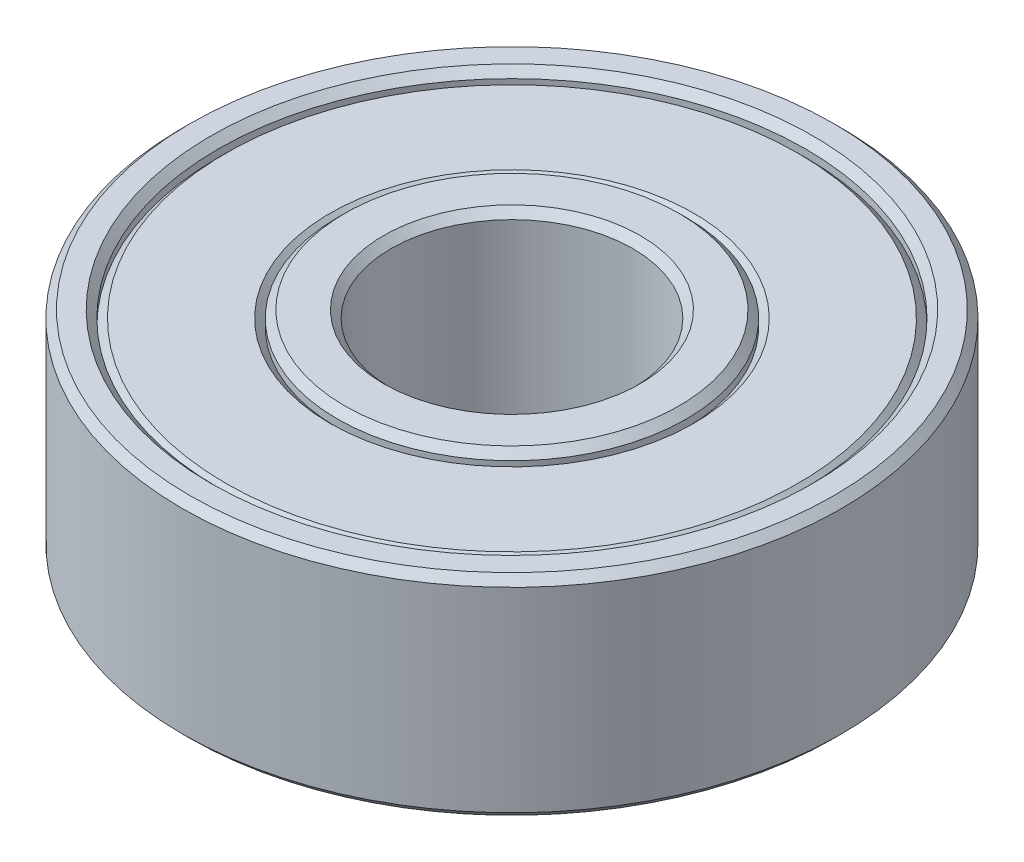
SolidWorks part; units mm, degrees
ref_plane "Front Plane" through (0, 0, 0) normal (0, 0, 1) x (1, 0, 0)
ref_plane "Top Plane" through (0, 0, 0) normal (0, 1, 0) x (1, 0, 0)
ref_plane "Right Plane" through (0, 0, 0) normal (1, 0, 0) x (0, 0, -1)
sketch "Sketch1" plane through (0, 0, 0) normal (0, 1, 0) x (1, 0, 0)
  circle A0 centre (0, 0) radius 10.975
  circle A1 centre (0, 0) radius 9.775
  circle A2 centre (0, 0) radius 5.81
  circle A3 centre (0, 0) radius 4.025
  dimension "D1" = 21.95
  dimension "D2" = 19.55
  dimension "D3" = 8.05
  dimension "D4" = 11.62
extrude "Boss-Extrude1" add sketch "Sketch1" along normal mid plane 7 contours A0 A1 | A2 A3 region at (-10.6646, 0, 0) region at (-5.6457, 0, 0)
extrude "Boss-Extrude2" add sketch "Sketch1<3>" along normal mid plane 6.5 separate body contours A1 A2 region at (-9.4985, 0, 0)
sketch "Sketch1<3>" plane through (0, 0, 0) normal (0, 1, 0) x (1, 0, 0) same geometry as "Sketch1"
chamfer "Chamfer1" distance 0.25 angle 45 4 edges at (0, -3.25, 5.81) (0, -3.25, 9.775) (0, 3.25, 5.81) (0, 3.25, 9.775)
chamfer "Chamfer2" distance 0.25 angle 45 4 edges at (0, -3.5, 9.775) (0, 3.5, 9.775) (0, -3.5, 10.975) (0, 3.5, 10.975)
chamfer "Chamfer3" distance 0.25 angle 45 4 edges at (0, 3.5, 5.81) (0, 3.5, 4.025) (0, -3.5, 4.025) (0, -3.5, 5.81)
combine bodies "Combine1" operation type add bodies to combine 103 102 101
